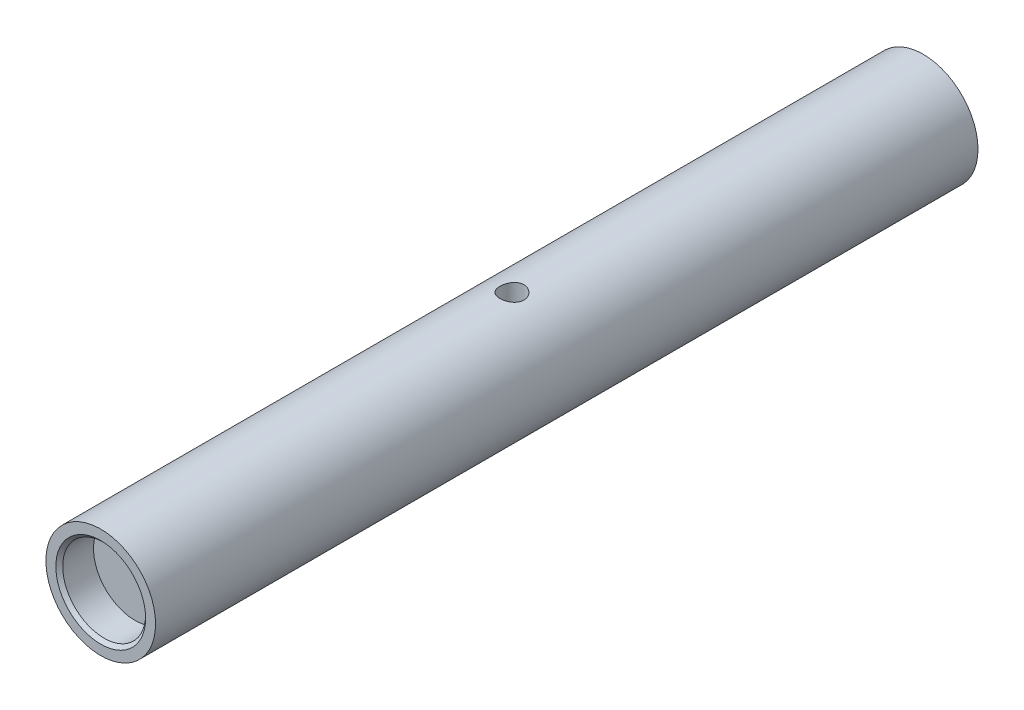
SolidWorks part; units mm, degrees
ref_plane "Front Plane" through (0, 0, 0) normal (0, 0, 1) x (1, 0, 0)
ref_plane "Top Plane" through (0, 0, 0) normal (0, 1, 0) x (1, 0, 0)
ref_plane "Right Plane" through (0, 0, 0) normal (1, 0, 0) x (0, 0, -1)
sketch "Sketch1" plane through (0, 0, 0) normal (0, 0, 1) x (1, 0, 0)
  circle A0 centre (0, 0) radius 4
  circle A1 centre (0, 0) radius 3.025
  dimension "D1" = 6.05
  dimension "D2" = 8
extrude "Boss-Extrude1" add sketch "Sketch1" along normal blind 60 contours A1 | A0 A1 | A1 | A0 region at (-3.8869, 0, 0) region at (0, 0, 0)
extrude "Cut-Extrude1" cut sketch "Sketch1<3>" along normal blind 2.5 contours A1 region at (0, 0, 0)
sketch "Sketch1<3>" plane through (0, 0, 0) normal (0, 0, 1) x (1, 0, 0) same geometry as "Sketch1"
extrude "Cut-Extrude2" cut sketch "Sketch1<4>" against normal blind 2.5 from surface contours A1 region at (0, 0, 0) starting at face at (4, 0, 60)
sketch "Sketch1<4>" plane through (0, 0, 0) normal (0, 0, 1) x (1, 0, 0) same geometry as "Sketch1"
chamfer "Chamfer1" distance 0.25 angle 45 2 edges at (3.025, 0, 0) (3.025, 0, 60)
sketch "Sketch2" plane through (0, 0, 0) normal (0, 1, 0) x (1, 0, 0)
  line L0 (4, -60) -> (4, 0) construction
  line L1 (4, -60) -> (4, 0) construction
  circle A0 centre (0, -30) radius 0.875
  point P4 (4, -30)
  point P5 (0, 0)
  dimension "D1" = 1.75
extrude "Cut-Extrude3" cut sketch "Sketch2" against normal through all and the other way through all
